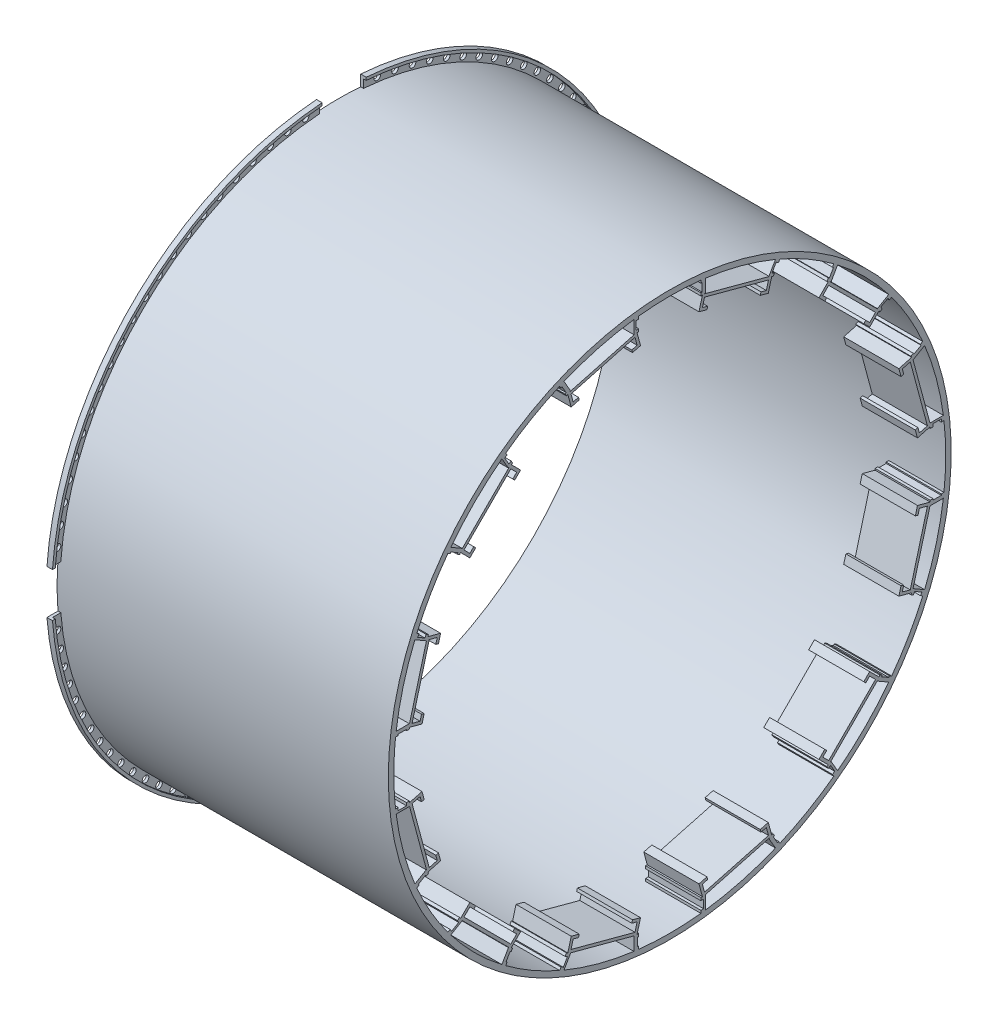
SolidWorks part; units mm, degrees
material "1.4122 (X39CrMo17-1)"
ref_plane "Ön Düzlem" through (0, 0, 0) normal (0, 0, 1) x (1, 0, 0)
ref_plane "Üst Düzlem" through (0, 0, 0) normal (0, 1, 0) x (1, 0, 0)
ref_plane "Sağ Düzlem" through (0, 0, 0) normal (1, 0, 0) x (0, 0, -1)
sketch "Çizim1" plane through (0, 0, 0) normal (0, 0, 1) x (1, 0, 0)
  line L0 (0, 0) -> (0, 30)
  line L1 (0, 30) -> (10, 30)
  line L2 (10, 30) -> (10, 25)
  line L3 (10, 25) -> (5, 25)
  line L4 (5, 25) -> (5, 10)
  line L5 (0, 0) -> (600, 0)
  line L6 (600, 0) -> (600, 10)
  line L11 (5, 10) -> (600, 10)
  dimension "D1" = 30
  dimension "D2" = 10
  dimension "D3" = 5
  dimension "D4" = 5
  dimension "D5" = 600
  dimension "D6" = 595
  dimension "D10" = 10
ref_plane "Düzlem1" through (0, -500, 0) normal (0, 1, 0) x (-1, 0, 0)
sketch "Çizim2" plane through (0, -500, 0) normal (0, 1, 0) x (-1, 0, 0)
  line L0 (0, 0) -> (-528.9975, 0) construction
revolve "Döndür1" add sketch "Çizim1" angle 360 about L0
sketch "Çizim3" plane through (0, 0, 0) normal (-1, 0, 0) x (0, 0, 1)
  line L0 (-40, 8.429) -> (-40, 28.4884)
  line L1 (40, 8.429) -> (40, 28.4884)
  line L2 (-40, -1008.429) -> (-40, -1028.4884)
  line L3 (40, -1008.429) -> (40, -1028.4884)
  line L4 (-528.4884, -540) -> (-508.429, -540)
  line L5 (-528.4884, -460) -> (-508.429, -460)
  line L6 (508.429, -460) -> (528.4884, -460)
  line L7 (508.429, -540) -> (528.4884, -540)
  circle A0 centre (0, -500) radius 510
  circle A1 centre (0, -500) radius 530 construction
  circle A2 centre (0, -500) radius 530
  point P19 (-510, -500)
  circle M2 centre (0, -500) radius 530
  dimension "D1" = 1020
  dimension "D4" = 1060
  dimension "D2" = 40
  dimension "D3" = 40
  dimension "D5" = 40
  dimension "D6" = 40
extrude "Kes-Ekstrüzyon1" cut sketch "Çizim3" against normal up to surface (600 mm away) contours A0 L1 L0 M2 | A0 L5 L4 M2 | A0 L2 L3 M2 | A0 L7 L6 M2 region at (0, 19.4861, 0) region at (0, -500, -519.4861) region at (0, -500, 519.4861) region at (0, -1019.4861, 0) up to face at (600, -500, 510)
sketch "Çizim4" plane through (0, 0, 0) normal (-1, 0, 0) x (0, 0, 1)
  circle A0 centre (0, 18.4587) radius 6
  circle A1 centre (32.5543, 17.4356) radius 6
  circle A2 centre (64.9801, 14.3705) radius 6
  circle A3 centre (97.1495, 9.2754) radius 6
  circle A4 centre (128.9354, 2.1703) radius 6
  circle A5 centre (160.2125, -6.9165) radius 6
  circle A6 centre (190.8574, -17.9493) radius 6
  circle A7 centre (220.749, -30.8846) radius 6
  circle A8 centre (249.7694, -45.6712) radius 6
  circle A9 centre (277.8041, -62.2509) radius 6
  circle A10 centre (304.7424, -80.5581) radius 6
  circle A11 centre (330.478, -100.5207) radius 6
  circle A12 centre (354.9094, -122.0599) radius 6
  circle A13 centre (377.9401, -145.0906) radius 6
  circle A14 centre (399.4793, -169.522) radius 6
  circle A15 centre (419.4419, -195.2576) radius 6
  circle A16 centre (437.7491, -222.1959) radius 6
  circle A17 centre (454.3288, -250.2306) radius 6
  circle A18 centre (469.1154, -279.251) radius 6
  circle A19 centre (482.0507, -309.1426) radius 6
  circle A20 centre (493.0835, -339.7875) radius 6
  circle A21 centre (502.1703, -371.0646) radius 6
  circle A22 centre (509.2754, -402.8505) radius 6
  circle A23 centre (514.3705, -435.0199) radius 6
  circle A24 centre (517.4356, -467.4457) radius 6
  circle A25 centre (518.4587, -500) radius 6
  circle A26 centre (517.4356, -532.5543) radius 6
  circle A27 centre (514.3705, -564.9801) radius 6
  circle A28 centre (509.2754, -597.1495) radius 6
  circle A29 centre (502.1703, -628.9354) radius 6
  circle A30 centre (493.0835, -660.2125) radius 6
  circle A31 centre (482.0507, -690.8574) radius 6
  circle A32 centre (469.1154, -720.749) radius 6
  circle A33 centre (454.3288, -749.7694) radius 6
  circle A34 centre (437.7491, -777.8041) radius 6
  circle A35 centre (419.4419, -804.7424) radius 6
  circle A36 centre (399.4793, -830.478) radius 6
  circle A37 centre (377.9401, -854.9094) radius 6
  circle A38 centre (354.9094, -877.9401) radius 6
  circle A39 centre (330.478, -899.4793) radius 6
  circle A40 centre (304.7424, -919.4419) radius 6
  circle A41 centre (277.8041, -937.7491) radius 6
  circle A42 centre (249.7694, -954.3288) radius 6
  circle A43 centre (220.749, -969.1154) radius 6
  circle A44 centre (190.8574, -982.0507) radius 6
  circle A45 centre (160.2125, -993.0835) radius 6
  circle A46 centre (128.9354, -1002.1703) radius 6
  circle A47 centre (97.1495, -1009.2754) radius 6
  circle A48 centre (64.9801, -1014.3705) radius 6
  circle A49 centre (32.5543, -1017.4356) radius 6
  circle A50 centre (0, -1018.4587) radius 6
  circle A51 centre (-32.5543, -1017.4356) radius 6
  circle A52 centre (-64.9801, -1014.3705) radius 6
  circle A53 centre (-97.1495, -1009.2754) radius 6
  circle A54 centre (-128.9354, -1002.1703) radius 6
  circle A55 centre (-160.2125, -993.0835) radius 6
  circle A56 centre (-190.8574, -982.0507) radius 6
  circle A57 centre (-220.749, -969.1154) radius 6
  circle A58 centre (-249.7694, -954.3288) radius 6
  circle A59 centre (-277.8041, -937.7491) radius 6
  circle A60 centre (-304.7424, -919.4419) radius 6
  circle A61 centre (-330.478, -899.4793) radius 6
  circle A62 centre (-354.9094, -877.9401) radius 6
  circle A63 centre (-377.9401, -854.9094) radius 6
  circle A64 centre (-399.4793, -830.478) radius 6
  circle A65 centre (-419.4419, -804.7424) radius 6
  circle A66 centre (-437.7491, -777.8041) radius 6
  circle A67 centre (-454.3288, -749.7694) radius 6
  circle A68 centre (-469.1154, -720.749) radius 6
  circle A69 centre (-482.0507, -690.8574) radius 6
  circle A70 centre (-493.0835, -660.2125) radius 6
  circle A71 centre (-502.1703, -628.9354) radius 6
  circle A72 centre (-509.2754, -597.1495) radius 6
  circle A73 centre (-514.3705, -564.9801) radius 6
  circle A74 centre (-517.4356, -532.5543) radius 6
  circle A75 centre (-518.4587, -500) radius 6
  circle A76 centre (-517.4356, -467.4457) radius 6
  circle A77 centre (-514.3705, -435.0199) radius 6
  circle A78 centre (-509.2754, -402.8505) radius 6
  circle A79 centre (-502.1703, -371.0646) radius 6
  circle A80 centre (-493.0835, -339.7875) radius 6
  circle A81 centre (-482.0507, -309.1426) radius 6
  circle A82 centre (-469.1154, -279.251) radius 6
  circle A83 centre (-454.3288, -250.2306) radius 6
  circle A84 centre (-437.7491, -222.1959) radius 6
  circle A85 centre (-419.4419, -195.2576) radius 6
  circle A86 centre (-399.4793, -169.522) radius 6
  circle A87 centre (-377.9401, -145.0906) radius 6
  circle A88 centre (-354.9094, -122.0599) radius 6
  circle A89 centre (-330.478, -100.5207) radius 6
  circle A90 centre (-304.7424, -80.5581) radius 6
  circle A91 centre (-277.8041, -62.2509) radius 6
  circle A92 centre (-249.7694, -45.6712) radius 6
  circle A93 centre (-220.749, -30.8846) radius 6
  circle A94 centre (-190.8574, -17.9493) radius 6
  circle A95 centre (-160.2125, -6.9165) radius 6
  circle A96 centre (-128.9354, 2.1703) radius 6
  circle A97 centre (-97.1495, 9.2754) radius 6
  circle A98 centre (-64.9801, 14.3705) radius 6
  circle A99 centre (-32.5543, 17.4356) radius 6
  dimension "D1" = 12
  dimension "D2" = 100
extrude "Kes-Ekstrüzyon2" cut sketch "Çizim4" against normal up to surface (600 mm away) up to face at (600, -500, 510)
ref_plane "Düzlem2" through (620, 0, 0) normal (1, 0, 0) x (0, 0, -1)
sketch "Çizim5" plane through (620, 0, 0) normal (1, 0, 0) x (0, 0, -1)
  line L0 (0, -500) -> (159.4622, 95.1212) construction
  line L1 (341, -500) -> (-341, -500) construction
  line L2 (0, 0) -> (0, -500) construction
  line L3 (59.1023, -47.6049) -> (68.7616, -50.1931)
  line L4 (-65, -3) -> (-65, -28)
  line L5 (-65, -3) -> (-56.35, -3)
  line L6 (-65, -28) -> (-56.35, -28)
  line L7 (-56.35, -28) -> (-56.35, -23)
  line L8 (-56.35, -23) -> (-61.35, -23)
  line L9 (-61.35, -23) -> (-61.35, -8)
  line L10 (-61.35, -8) -> (-56.35, -8)
  line L11 (-56.35, -8) -> (-56.35, -3)
  line L12 (56.35, -8) -> (58.65, -8)
  line L13 (56.35, -28) -> (56.35, -23)
  line L14 (65, -3) -> (56.35, -3)
  line L15 (56.35, -8) -> (56.35, -3)
  line L16 (58.65, -8) -> (58.65, -23)
  line L17 (58.65, -23) -> (56.35, -23)
  line L18 (65, -3) -> (65, -28)
  line L19 (59.4491, -26.9923) -> (185.0194, -60.6388)
  line L20 (65, -28) -> (63.2098, -28)
  line L21 (68.7616, -50.1931) -> (67.4675, -55.0227)
  line L22 (67.4675, -55.0227) -> (52.9786, -51.1405)
  line L23 (52.9786, -51.1405) -> (59.4491, -26.9923)
  line L24 (59.1023, -47.6049) -> (62.9846, -33.116)
  line L25 (62.9846, -33.116) -> (178.8957, -64.1743)
  line L26 (165.3542, -76.075) -> (164.0601, -80.9047)
  line L27 (164.0601, -80.9047) -> (178.549, -84.7869)
  line L28 (175.0134, -78.6632) -> (165.3542, -76.075)
  line L29 (175.0134, -78.6632) -> (178.8957, -64.1743)
  line L30 (178.549, -84.7869) -> (185.0194, -60.6388)
  line L31 (59.1791, -28) -> (56.35, -28)
  point P23 (120.9402, -48.6452)
  point P30 (122.2343, -43.8156)
  point P36 (120.9402, -48.6452)
  point P38 (122.2343, -43.8156)
  dimension "D1" = 15
  dimension "D2" = 65
  dimension "D3" = 5
  dimension "D4" = 3
  dimension "D5" = 25
  dimension "D6" = 60
  dimension "D7" = 61.35
  dimension "D8" = 15
  dimension "D9" = 5
  dimension "D10" = 5
  dimension "D11" = 5
  dimension "D12" = 15
  dimension "D13" = 15
  dimension "D14" = 5
  dimension "D15" = 58.65
extrude "Yükseklik-Ekstrüzyon1" add sketch "Çizim5" against normal blind 100 from offset 20 contours L4 L6 L7 L8 L9 L10 L11 L5 offset against normal yes
extrude "Yükseklik-Ekstrüzyon2" add sketch "Çizim5<3>" against normal blind 100 from offset 20 contours L18 L14 L15 L12 L13 | L27 L19 L21 L22 L24 L25 region at (620, -50.2913, -63.5589) region at (620, -15.3625, -61.2852) offset against normal yes
sketch "Çizim5<3>" plane through (620, 0, 0) normal (1, 0, 0) x (0, 0, -1) same geometry as "Çizim5"
pattern_circular "Dairesel Çoğaltma8" count 12 over 360 about axis through (600, -500, 0) along (-1, 0, 0) of "Yükseklik-Ekstrüzyon2"
pattern_circular "Dairesel Çoğaltma9" count 12 over 360 about axis through (600, -500, 0) along (-1, 0, 0) of "Yükseklik-Ekstrüzyon1"
